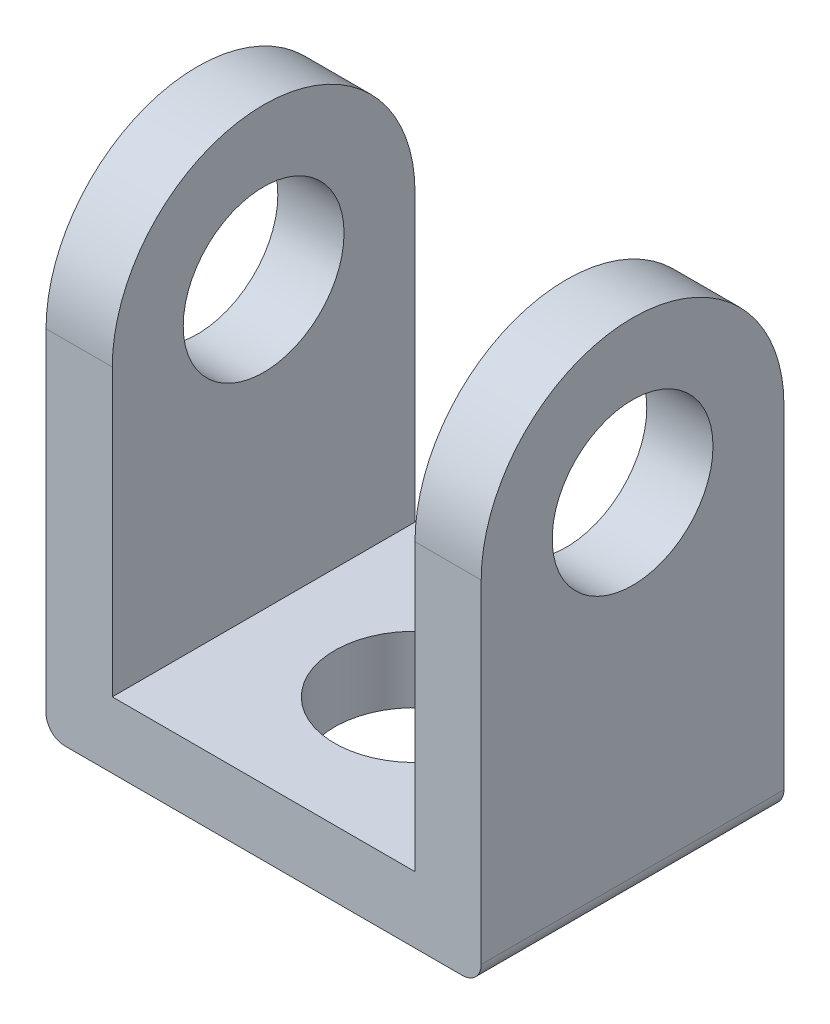
SolidWorks part; units mm, degrees
ref_plane "Front Plane" through (0, 0, 0) normal (0, 0, 1) x (1, 0, 0)
ref_plane "Top Plane" through (0, 0, 0) normal (0, 1, 0) x (1, 0, 0)
ref_plane "Right Plane" through (0, 0, 0) normal (1, 0, 0) x (0, 0, -1)
sketch "Sketch1" plane through (0, 0, 0) normal (0, 1, 0) x (1, 0, 0)
  line L0 (-5.75, -4) -> (5.75, -4)
  line L1 (-5.75, -4) -> (-5.75, 4)
  line L2 (5.75, -4) -> (5.75, 4)
  line L3 (-5.75, 4) -> (5.75, 4)
  line L4 (-5.75, -4) -> (5.75, 4) construction
  line L5 (5.75, -4) -> (-5.75, 4) construction
  point P1 (0, 0)
  dimension "D1" = 11.5
  dimension "D2" = 8
extrude "Boss-Extrude1" add sketch "Sketch1" along normal blind 13.3
sketch "Sketch2" plane through (5.75, 0, 0) normal (1, 0, 0) x (0, 0, -1)
  line L0 (-4, 0) -> (4, 0) construction
  circle A0 centre (0, 9.3) radius 2.125
  point P2 (0, 0)
  dimension "D2" = 4.25
  dimension "D1" = 9.3
extrude "Cut-Extrude1" cut sketch "Sketch2" against normal up to next
sketch "Sketch3" plane through (5.75, 0, 0) normal (1, 0, 0) x (0, 0, -1)
  line L0 (-4, 13.3) -> (-4, 0) construction
  line L1 (-4, 13.3) -> (4, 13.3) construction
  line L2 (4, 13.3) -> (4, 0) construction
  line L3 (-4, 13.3) -> (-4, 9.3)
  line L4 (-4, 13.3) -> (4, 13.3)
  line L5 (4, 13.3) -> (4, 9.3)
  circle A2 centre (0, 9.3) radius 4
  arc A3 (4, 9.3) -> (-4, 9.3) centre (0, 9.3) ccw
  line M4 (4, 0) -> (4, 13.3)
  line M5 (4, 13.3) -> (-4, 13.3)
  line M6 (-4, 13.3) -> (-4, 0)
  dimension "D1" = 1.875
extrude "Cut-Extrude2" cut sketch "Sketch3" against normal up to next contours A3 M4 M5 | A3 L4 M6 region at (5.75, 12.4065, 3.1065) region at (5.75, 12.4065, -3.1065)
sketch "Sketch4" plane through (0, 0, 4) normal (0, 0, 1) x (1, 0, 0)
  line L8 (5.75, 13.3) -> (-5.75, 13.3) construction
  line L9 (4, 13.3) -> (-4, 13.3)
  line L11 (-4, 9.3) -> (-4, 1.75)
  line L12 (4, 1.75) -> (4, 9.3)
  line L13 (-4, 1.75) -> (4, 1.75)
  line L14 (-4, 13.3) -> (-4, 1.75)
  line L15 (4, 1.75) -> (4, 13.3)
  line L16 (-4, 1.75) -> (4, 1.75)
  dimension "D1" = 1.75
extrude "Cut-Extrude3" cut sketch "Sketch4" against normal up to next
sketch "Sketch5" plane through (0, 0, 0) normal (0, -1, 0) x (1, 0, 0)
  circle A0 centre (0, 0) radius 2.125
extrude "Cut-Extrude4" cut sketch "Sketch5" against normal up to next
fillet "Fillet1" radius 0.5 2 edges at (5.75, 0, 0) (-5.75, 0, 0)
